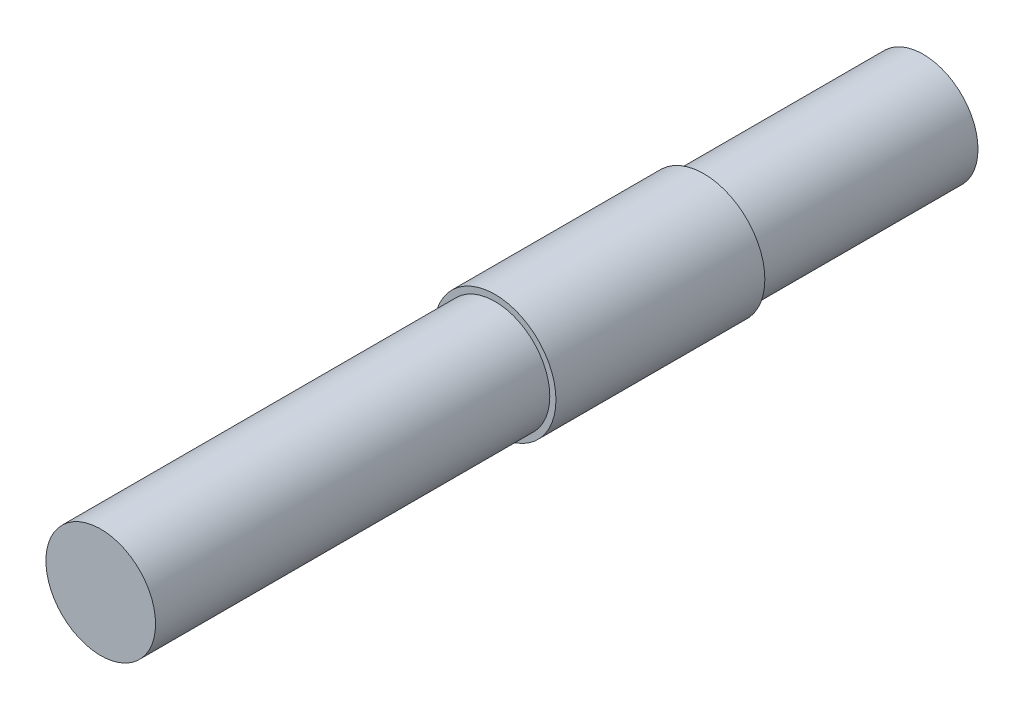
SolidWorks part; units mm, degrees
ref_plane "Front Plane" through (0, 0, 0) normal (0, 0, 1) x (1, 0, 0)
ref_plane "Top Plane" through (0, 0, 0) normal (0, 1, 0) x (1, 0, 0)
ref_plane "Right Plane" through (0, 0, 0) normal (1, 0, 0) x (0, 0, -1)
sketch "Sketch1" plane through (0, 0, 0) normal (0, 0, 1) x (1, 0, 0)
  circle A0 centre (0, 0) radius 5.5626
  dimension "D1" = 11.1252
extrude "Boss-Extrude1" add sketch "Sketch1" along normal blind 75 contours A0
ref_plane "Plane1" through (0, 0, 20) normal (0, 0, 1) x (1, 0, 0)
ref_plane "Plane2" through (0, 0, 39.05) normal (0, 0, 1) x (1, 0, 0)
sketch "Sketch5" plane through (0, 0, 20) normal (0, 0, 1) x (1, 0, 0)
  circle A0 centre (0, 0) radius 5
  circle A1 centre (0, 0) radius 5.5626
  dimension "D1" = 10
extrude "Cut-Extrude2" cut sketch "Sketch5" against normal up to surface (20 mm away) up to face at (5.5626, 0, 0)
sketch "Sketch6" plane through (0, 0, 39.05) normal (0, 0, 1) x (1, 0, 0)
  circle A0 centre (0, 0) radius 5.5626 construction
  circle A1 centre (0, 0) radius 5 construction
  circle A2 centre (0, 0) radius 5.5626
  circle A3 centre (0, 0) radius 5
extrude "Cut-Extrude3" cut sketch "Sketch6" along normal up to surface (35.95 mm away) up to face at (5.5626, 0, 75)
